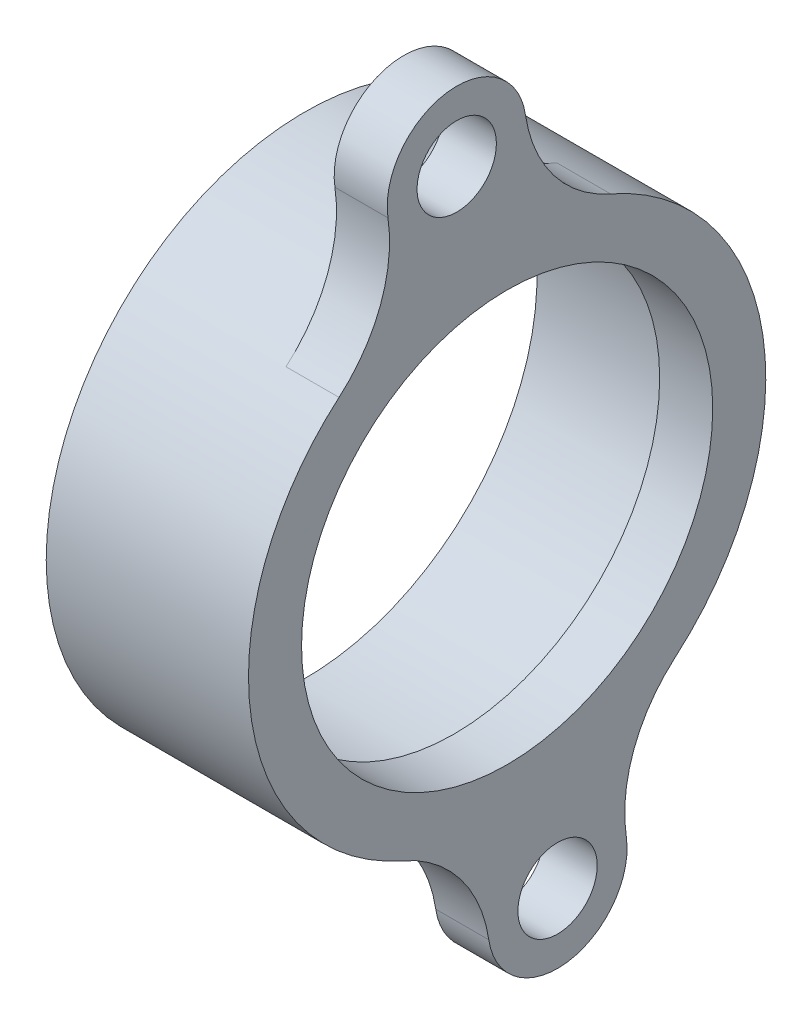
SolidWorks part; units mm, degrees
ref_plane "Front Plane" through (0, 0, 0) normal (0, 0, 1) x (1, 0, 0)
ref_plane "Top Plane" through (0, 0, 0) normal (0, 1, 0) x (1, 0, 0)
ref_plane "Right Plane" through (0, 0, 0) normal (1, 0, 0) x (0, 0, -1)
sketch "Sketch1" plane through (0, 0, 0) normal (0, 0, 1) x (1, 0, 0)
  line L0 (24.6062, 12.3825) -> (31.75, 12.3825)
  line L1 (31.75, 12.3825) -> (31.75, 11.1125)
  line L2 (31.75, 11.1125) -> (24.6062, 11.1125)
  line L4 (24.6062, 11.1125) -> (24.6062, 12.3825)
  line L5 (0, 0) -> (40.0174, 0) construction
  dimension "D1" = 1.27
  dimension "D2" = 7.1437
revolve "Revolve1" add sketch "Sketch1" angle 360 about L5
sketch "Sketch2" plane through (31.75, 0, 0) normal (1, 0, 0) x (0, 0, -1)
  line L0 (3.7, -24.7915) -> (-3.7, 24.7915) construction
  line L1 (-5.7046, 15.681) -> (0.8773, 16.6633) construction
  line L2 (-11.5595, -1.7252) -> (11.5595, 1.7252) construction
  line L4 (-4.094, 11.9086) -> (0.4385, 12.5851) construction
  line L5 (0.4385, 12.5851) -> (2.1189, 16.8486) construction
  line L6 (2.1189, 16.8486) -> (-0.7332, 20.4356) construction
  line L7 (-0.7332, 20.4356) -> (-5.2657, 19.7592) construction
  line L8 (-5.2657, 19.7592) -> (-6.9461, 15.4957) construction
  line L9 (-6.9461, 15.4957) -> (-4.094, 11.9086) construction
  arc A0 (-8.0474, 9.4109) -> (-4.9489, -11.3505) centre (0, 0) ccw
  circle A1 centre (0, 0) radius 12.3825 construction
  arc A7 (0.8773, 16.6633) -> (-5.7046, 15.681) centre (-2.4136, 16.1721) ccw
  arc A8 (-8.0474, 9.4109) -> (-5.7046, 15.681) centre (-12.5371, 14.6613) ccw
  arc A9 (0.8773, 16.6633) -> (4.9489, 11.3505) centre (7.7099, 17.683) ccw
  circle A10 centre (0, 0) radius 9.8425
  circle A11 centre (0, 0) radius 11.1125 construction
  arc A12 (5.7046, -15.681) -> (8.0474, -9.4109) centre (12.5371, -14.6613) cw
  arc A14 (5.7046, -15.681) -> (-0.8773, -16.6633) centre (2.4136, -16.1721) cw
  arc A15 (-4.9489, -11.3505) -> (-0.8773, -16.6633) centre (-7.7099, -17.683) cw
  arc A16 (8.0474, -9.4109) -> (4.9489, 11.3505) centre (0, 0) ccw
  circle A17 centre (-2.4136, 16.1721) radius 3.9688 construction
  arc A18 (1.509, 20.9354) -> (-7.5561, 19.5825) centre (-3.0235, 20.259) ccw construction
  arc A19 (-1.509, -20.9354) -> (7.5561, -19.5825) centre (3.0235, -20.259) ccw construction
  dimension "D1" = 1.27
  dimension "D2" = 3.3274
  dimension "D3" = 7.9375
extrude "Boss-Extrude1" add sketch "Sketch2" along normal blind 2.54
hole_wizard "#6 Clearance Hole1" positions "Sketch3" profile "Sketch5" hole size "#6" standard "ANSI Inch" end condition up to next
sketch "Sketch3" plane through (34.29, 0, 0) normal (1, 0, 0) x (0, 0, -1)
  point P0 (-2.4136, 16.1721)
  point P3 (2.4136, -16.1721)
sketch "Sketch5" plane through (34.29, 16.1721, 2.4136) normal (0, 1, 0) x (0, 0, -1)
  line L0 (0, 0) -> (0, 2.54)
  line L1 (0, 2.54) -> (1.8986, 2.54)
  line L2 (1.8986, 2.54) -> (1.8986, 0)
  line L5 (1.8986, 0) -> (0, 0)
  line L11 (0, -6.35) -> (0, 107.95) construction
  dimension "Thru Hole Dia." = 3.7973
  dimension "Thru Hole Depth" = 2.54
